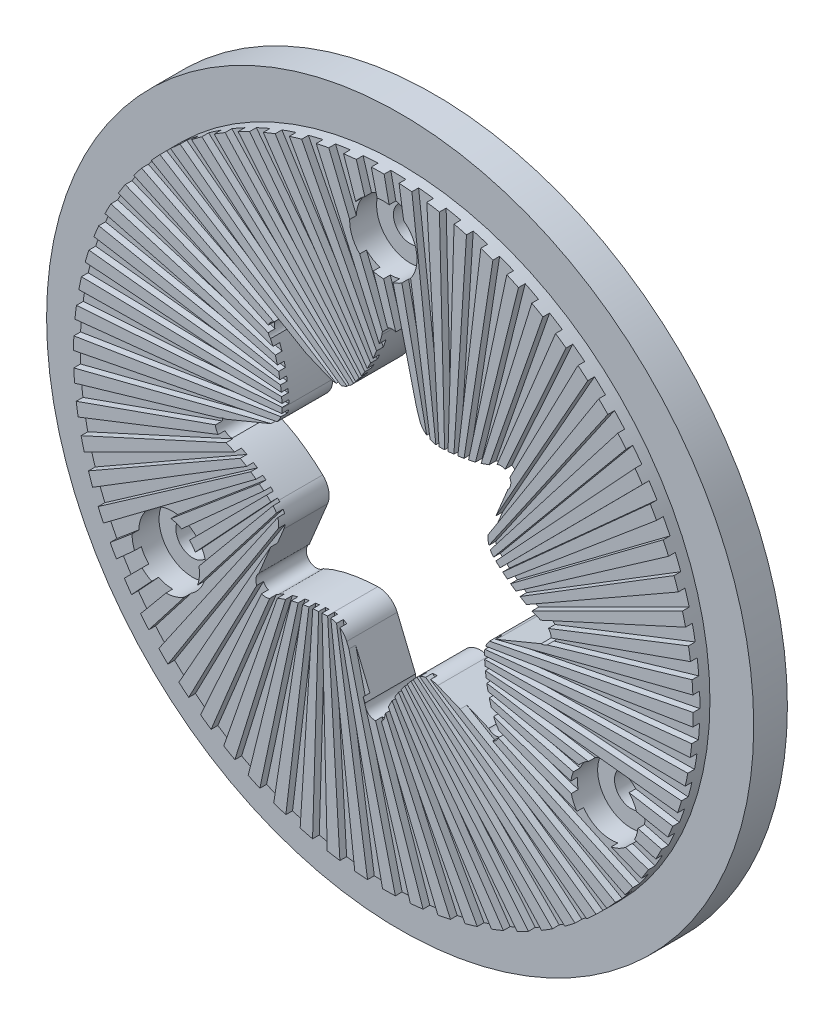
SolidWorks part; units mm, degrees
material "Aleación 1060"
ref_plane "Alzado" through (0, 0, 0) normal (0, 0, 1) x (1, 0, 0)
ref_plane "Planta" through (0, 0, 0) normal (0, 1, 0) x (1, 0, 0)
ref_plane "Vista lateral" through (0, 0, 0) normal (1, 0, 0) x (0, 0, -1)
sketch "Croquis1" plane through (0, 0, 0) normal (0, 0, 1) x (1, 0, 0)
  circle A0 centre (0, 0) radius 52.5
  dimension "D1" = 105
extrude "Saliente-Extruir1" add sketch "Croquis1" along normal blind 5
sketch "Croquis2" plane through (0, 0, 5) normal (0, 0, 1) x (1, 0, 0)
  line L0 (-21.561, 40.6463) -> (-1.4614, 16.1841)
  line L254 (-18.0362, 42.3284) -> (-18.0298, 42.3193)
  line L255 (-0.5, 16.2423) -> (-19.8542, 41.4947)
  arc A1 (-19.8542, 41.4947) -> (-21.5539, 40.6378) centre (0, 0) ccw
  arc A10 (-0.5, 16.2423) -> (-1.4614, 16.1841) centre (0, 0) ccw
extrude "Saliente-Extruir2" add sketch "Croquis2" along normal blind 2.5 contours A10 L255 A1 L0 region at (-12.1758, 30.3231, 5)
pattern_circular "MatrizC1" count 70 over 360 about axis through (0, 0, 5) along (0, 0, -1) of "Saliente-Extruir2"
sketch "Croquis3" plane through (0, 0, 5) normal (0, 0, 1) x (1, 0, 0)
  circle A0 centre (0, 0) radius 46
extrude "Saliente-Extruir3" add sketch "Croquis3" along normal blind 1.5
sketch "Croquis6" plane through (0, 0, 7.5) normal (0, 0, 1) x (1, 0, 0)
  line L1 (0, 0) -> (0, 37.5) construction
  line L2 (0, -52.5) -> (0, 52.5) construction
  line L4 (-16.0282, -2.6757) -> (-38.4541, -25.2445) construction
  circle A0 centre (0, 37.5) radius 5
  circle A1 centre (0, 0) radius 37.5 construction
  circle A2 centre (0, 0) radius 52.5 construction
  circle A3 centre (32.8248, -18.7484) radius 5
  circle A4 centre (-32.3001, -19.0513) radius 5
  point P10 (0, 0)
  point P17 (0.1749, -0.0999)
  dimension "D1" = 75
  dimension "D3" = 10
  dimension "D2" = 360
  dimension "D4" = 3
extrude "Cortar-Extruir4" cut sketch "Croquis6" against normal blind 4
sketch "Croquis5" plane through (0, 0, 5) normal (0, 0, 1) x (1, 0, 0)
  line L0 (14.6462, -18.4931) -> (8.0792, -15.7729)
  line L1 (2.7642, 25.1886) -> (5.3549, 17.0991)
  line L2 (-14.6462, 18.4931) -> (-8.0792, 15.7729)
  line L3 (-16.866, 5.4403) -> (-23.433, 2.7201)
  line L4 (-5.4403, -16.866) -> (-2.7201, -23.433)
  line L5 (-15.7729, -8.0792) -> (-18.4931, -14.6462)
  line L6 (23.433, -2.7201) -> (16.866, -5.4403)
  line L7 (18.4931, 14.6462) -> (15.7729, 8.0792)
  arc A0 (-15.7729, -8.0792) -> (-16.5037, -4.7323) centre (-18.5446, -6.9312) ccw
  arc A1 (-8.3237, -15.0161) -> (-5.4403, -16.866) centre (-8.2119, -18.014) cw
  arc A2 (4.7323, -16.5037) -> (8.0792, -15.7729) centre (6.9312, -18.5446) cw
  arc A3 (15.0161, -8.3237) -> (16.866, -5.4403) centre (18.014, -8.2119) cw
  arc A4 (16.5037, 4.7323) -> (15.7729, 8.0792) centre (18.5446, 6.9312) cw
  arc A5 (8.3237, 15.0161) -> (5.3549, 17.0991) centre (8.2119, 18.014) cw
  arc A6 (-8.0792, 15.7729) -> (-4.7323, 16.5037) centre (-6.9312, 18.5446) ccw
  arc A7 (-16.866, 5.4403) -> (-15.0161, 8.3237) centre (-18.014, 8.2119) ccw
  arc A8 (-0.189, 25.2064) -> (2.7642, 25.1886) centre (1.2876, 25.1975) cw
  arc A9 (16.4174, 16.747) -> (18.4931, 14.6462) centre (17.4552, 15.6966) cw
  arc A10 (-16.747, 16.4174) -> (-14.6462, 18.4931) centre (-15.6966, 17.4552) cw
  arc A11 (-23.4508, -0.2331) -> (-23.433, 2.7201) centre (-23.4419, 1.2435) cw
  arc A12 (-16.4174, -16.747) -> (-18.4931, -14.6462) centre (-17.4552, -15.6966) cw
  arc A13 (0.2331, -23.4508) -> (-2.7201, -23.433) centre (-1.2435, -23.4419) cw
  arc A14 (16.747, -16.4174) -> (14.6462, -18.4931) centre (15.6966, -17.4552) cw
  arc A15 (23.4508, 0.2331) -> (23.433, -2.7201) centre (23.4419, -1.2435) cw
  spline S0 degree 3 poles (-16.747, 16.4174) (-15.7142, 14.2692) (-15.1372, 11.5713) (-15.0161, 8.3237) knots 0.45265 0.45265 0.45265 0.45265 0.9053 0.9053 0.9053 0.9053
  spline S1 degree 3 poles (16.4174, 16.747) (14.2692, 15.7142) (11.5713, 15.1372) (8.3237, 15.0161) knots 0.45265 0.45265 0.45265 0.45265 0.9053 0.9053 0.9053 0.9053
  spline S3 degree 3 poles (23.4508, 0.2331) (21.2014, 1.0218) (18.8857, 2.5215) (16.5037, 4.7323) knots 0.45265 0.45265 0.45265 0.45265 0.9053 0.9053 0.9053 0.9053
  spline S4 degree 3 poles (16.747, -16.4174) (15.7142, -14.2692) (15.1372, -11.5713) (15.0161, -8.3237) knots 0.45265 0.45265 0.45265 0.45265 0.9053 0.9053 0.9053 0.9053
  spline S5 degree 3 poles (0.2331, -23.4508) (1.0218, -21.2014) (2.5215, -18.8857) (4.7323, -16.5037) knots 0.45265 0.45265 0.45265 0.45265 0.9053 0.9053 0.9053 0.9053
  spline S6 degree 3 poles (-16.4174, -16.747) (-14.2692, -15.7142) (-11.5713, -15.1372) (-8.3237, -15.0161) knots 0.45265 0.45265 0.45265 0.45265 0.9053 0.9053 0.9053 0.9053
  spline S7 degree 3 poles (-23.4508, -0.2331) (-21.2014, -1.0218) (-18.8857, -2.5215) (-16.5037, -4.7323) knots 0.45265 0.45265 0.45265 0.45265 0.9053 0.9053 0.9053 0.9053
  spline S8 degree 3 poles (-0.189, 25.2064) (-1.0211, 22.1375) (-2.5215, 18.8857) (-4.7323, 16.5037) knots 0.45265 0.45265 0.45265 0.45265 0.9053 0.9053 0.9053 0.9053
  dimension "D1" = 3
extrude "Cortar-Extruir3" cut sketch "Croquis5" against normal mid plane 90.5
sketch "Croquis7" plane through (0, 0, 0) normal (0, 0, -1) x (-1, 0, 0)
  circle A0 centre (0, 37.5) radius 2.5
  circle A1 centre (32.3001, -19.0513) radius 2.5
  circle A2 centre (-32.8248, -18.7484) radius 2.5
  dimension "D1" = 5
extrude "Cortar-Extruir5" cut sketch "Croquis7" against normal through all
